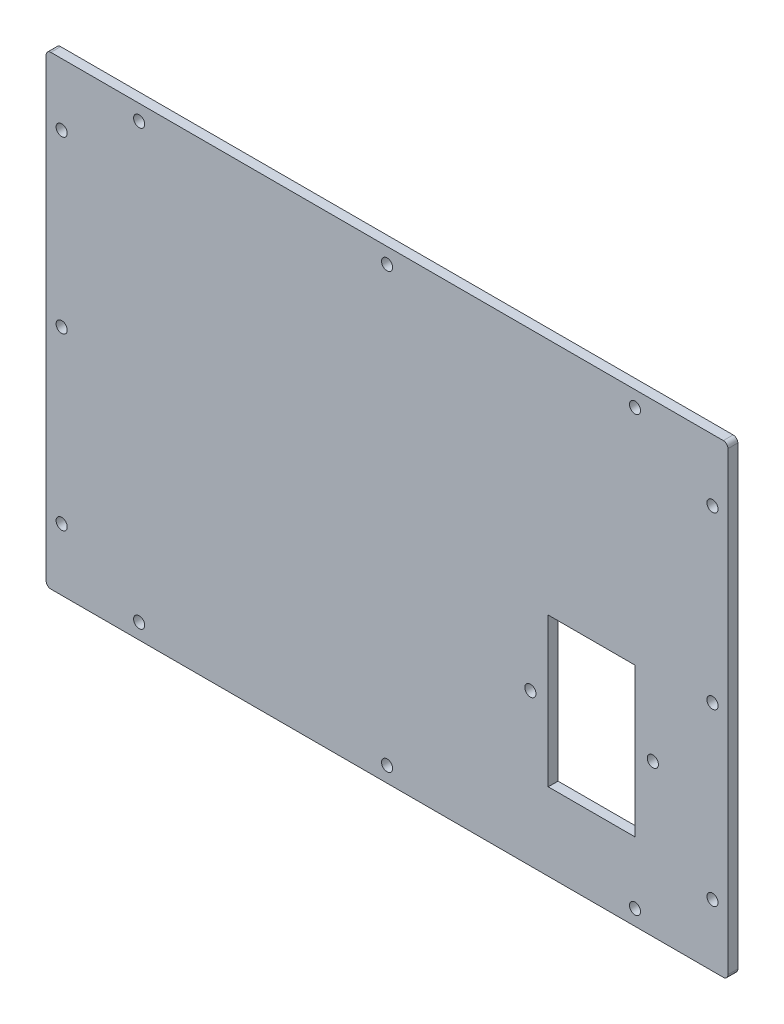
SolidWorks part; units mm, degrees
ref_plane "Front Plane" through (0, 0, 0) normal (0, 0, 1) x (1, 0, 0)
ref_plane "Top Plane" through (0, 0, 0) normal (0, 1, 0) x (1, 0, 0)
ref_plane "Right Plane" through (0, 0, 0) normal (1, 0, 0) x (0, 0, -1)
sketch "Sketch1" plane through (0, 0, 0) normal (0, 0, 1) x (1, 0, 0)
  line L0 (0, 0) -> (0, 75) construction
  line L1 (-110, -75) -> (110, -75)
  line L2 (-110, -75) -> (-110, 75)
  line L3 (-110, 75) -> (110, 75)
  line L4 (110, -75) -> (110, 75)
  line L5 (-110, -75) -> (110, 75) construction
  line L6 (-110, 75) -> (110, -75) construction
  line L15 (0, 0) -> (-110, 0) construction
  point P0 (0, 0)
  dimension "D1" = 220
  dimension "D2" = 150
extrude "Boss-Extrude1" add sketch "Sketch1" along normal blind 3.175 contours L3 L2 L1 L4 region at (0, 0, 0)
hole_wizard "M3 Clearance Hole1" positions "Sketch2" profile "Sketch3" hole size "M3" standard "ANSI Metric" end condition through all
sketch "Sketch2" plane through (0, 0, 3.175) normal (0, 0, 1) x (1, 0, 0)
  line L1 (-105, -70) -> (105, -70)
  line L2 (-105, -70) -> (-105, 70)
  line L3 (-105, 70) -> (105, 70)
  line L4 (105, -70) -> (105, 70)
  line L5 (-105, -70) -> (105, 70) construction
  line L6 (-105, 70) -> (105, -70) construction
  line L7 (-110, -75) -> (-110, 75) construction
  line L8 (-110, 75) -> (110, 75) construction
  point P2 (0, 0)
  point P113 (-80, 70)
  point P115 (80, 70)
  point P116 (0, 70)
  point P118 (-105, 55)
  point P120 (-105, 0)
  point P122 (-105, -55)
  point P124 (-80, -70)
  point P126 (0, -70)
  point P128 (80, -70)
  point P130 (105, -55)
  point P132 (105, 0)
  point P134 (105, 55)
  dimension "D1" = 5
  dimension "D2" = 5
  dimension "D3" = 80
  dimension "D4" = 80
  dimension "D5" = 55
  dimension "D6" = 55
sketch "Sketch3" plane through (0, 0, 3.175) normal (1, 0, 0) x (0, -1, 0)
  line L0 (0, 0) -> (0, 3.175)
  line L1 (0, 3.175) -> (1.8, 3.175)
  line L2 (1.8, 3.175) -> (1.8, 0)
  line L5 (1.8, 0) -> (0, 0)
  line L11 (0, -6.35) -> (0, 107.95) construction
  dimension "Thru Hole Dia." = 3.6
  dimension "Thru Hole Depth" = 3.175
sketch "Sketch4" plane through (0, 0, 3.175) normal (0, 0, 1) x (1, 0, 0)
  line L1 (-5, -5) -> (5, -5)
  line L2 (-5, -5) -> (-5, 5)
  line L3 (-5, 5) -> (5, 5)
  line L4 (5, -5) -> (5, 5)
  line L5 (-5, -5) -> (5, 5) construction
  line L6 (-5, 5) -> (5, -5) construction
  point P0 (0, 0)
  dimension "D1" = 10
  dimension "D2" = 10
extrude "Boss-Extrude2" add sketch "Sketch4" against normal through all
fillet "Fillet2" radius 1.5 4 edges at (-110, -75, 1.5875) (110, -75, 1.5875) (110, 75, 1.5875) (-110, 75, 1.5875)
sketch "Sketch5" plane through (0, 0, 3.175) normal (0, 0, 1) x (1, 0, 0)
  line L0 (46.25, -26) -> (85.75, -26) construction
  line L1 (52, -50) -> (80, -50)
  line L2 (52, -50) -> (52, -2)
  line L3 (52, -2) -> (80, -2)
  line L4 (80, -50) -> (80, -2)
  line L5 (52, -50) -> (80, -2) construction
  line L6 (52, -2) -> (80, -50) construction
  line L7 (-108.5, -75) -> (108.5, -75) construction
  line L8 (110, -73.5) -> (110, 73.5) construction
  line L10 (-90, -60) -> (30, -60)
  line L11 (-90, -60) -> (-90, 60)
  line L12 (-90, 60) -> (30, 60)
  line L13 (30, -60) -> (30, 60)
  line L14 (-90, -60) -> (30, 60) construction
  line L15 (-90, 60) -> (30, -60) construction
  line L16 (-110, -73.5) -> (-110, 73.5) construction
  point P0 (66, -26)
  point P8 (66, -26)
  point P12 (-30, 0)
  dimension "D1" = 28
  dimension "D2" = 48
  dimension "D3" = 39.5
  dimension "D4" = 25
  dimension "D5" = 30
  dimension "D6" = 120
  dimension "D7" = 120
  dimension "D8" = 15
  dimension "D9" = 20
extrude "Cut-Extrude1" cut sketch "Sketch5" against normal through all contours L1 L4 L3 L2 region at (66, -26, 3.175)
hole_wizard "M3 Clearance Hole2" positions "Sketch6" profile "Sketch7" hole size "M3" standard "ANSI Metric" end condition through all
sketch "Sketch6" plane through (0, 0, 3.175) normal (0, 0, 1) x (1, 0, 0)
  point P0 (46.25, -26)
  point P3 (85.75, -26)
sketch "Sketch7" plane through (46.25, -26, 3.175) normal (1, 0, 0) x (0, -1, 0)
  line L0 (0, 0) -> (0, 3.175)
  line L1 (0, 3.175) -> (1.8, 3.175)
  line L2 (1.8, 3.175) -> (1.8, 0)
  line L5 (1.8, 0) -> (0, 0)
  line L11 (0, -6.35) -> (0, 107.95) construction
  dimension "Thru Hole Dia." = 3.6
  dimension "Thru Hole Depth" = 3.175
